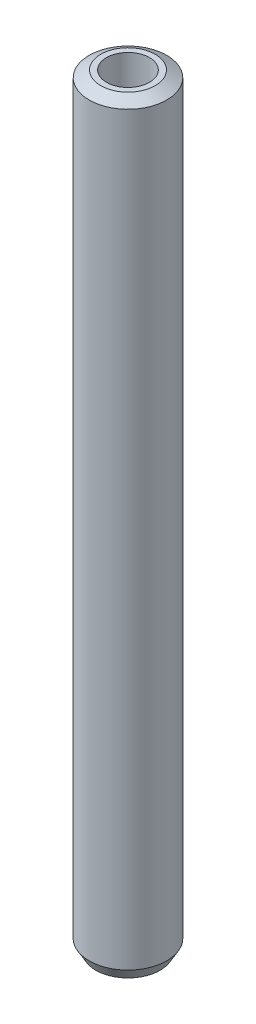
SolidWorks part; units mm, degrees
ref_plane "Front Plane" through (0, 0, 0) normal (0, 0, 1) x (1, 0, 0)
ref_plane "Top Plane" through (0, 0, 0) normal (0, 1, 0) x (1, 0, 0)
ref_plane "Right Plane" through (0, 0, 0) normal (1, 0, 0) x (0, 0, -1)
sketch "Sketch1" plane through (0, 0, 0) normal (0, 1, 0) x (1, 0, 0)
  circle A0 centre (0, 0) radius 12.5
  dimension "SHAFT_OD" = 25
extrude "Boss-Extrude1" add sketch "Sketch1" along normal blind 246.2832
sketch "Sketch2" plane through (0, 0, 0) normal (0, 1, 0) x (1, 0, 0)
  circle A0 centre (0, 0) radius 6.9292
  dimension "BORE_D" = 13.8583
extrude "Cut-Extrude1" cut sketch "Sketch2" along normal through all
chamfer "Chamfer1" distance 2.1497 angle 60 2 edges at (0, 246.2832, 12.5) (0, 0, 12.5) first distance on face at (0, 246.2832, 12.5) first distance on face at (0, 0, 6.9292)
